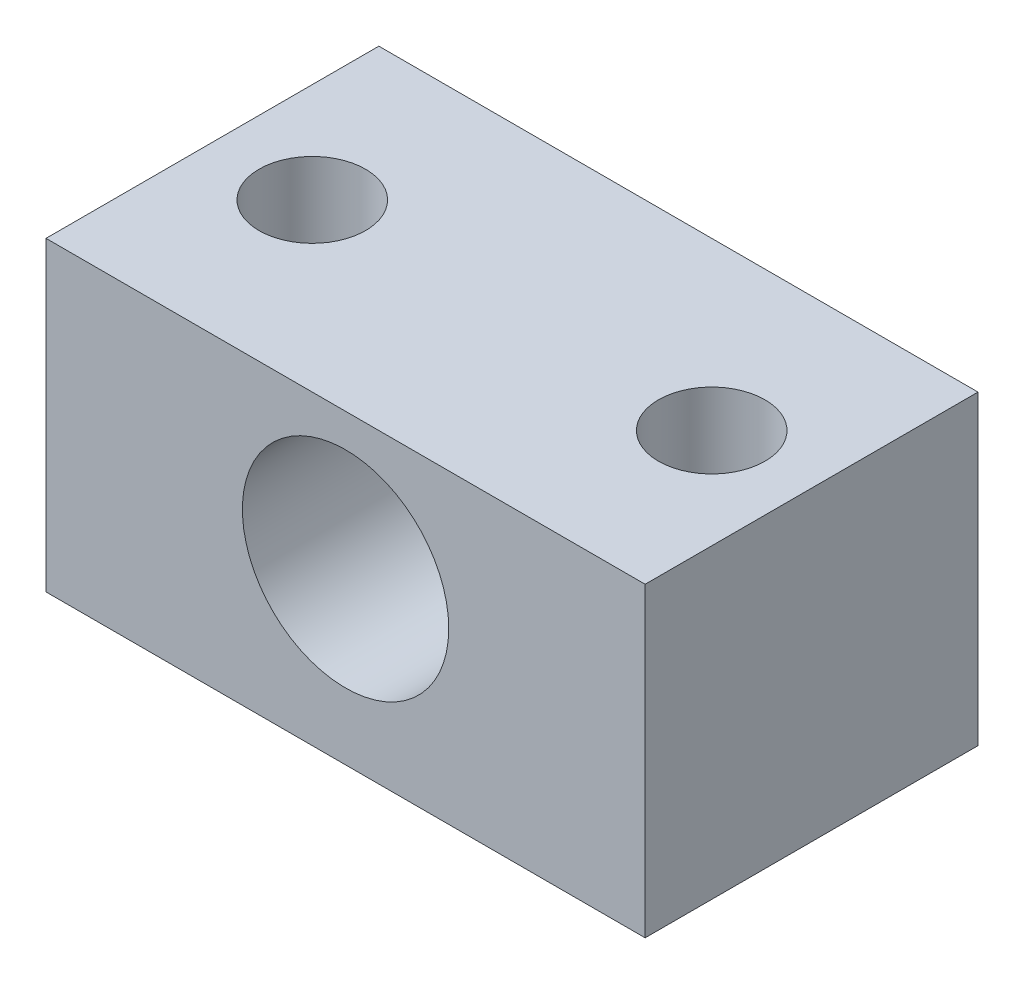
SolidWorks part; units mm, degrees
ref_plane "正面" through (0, 0, 0) normal (0, 0, 1) x (1, 0, 0)
ref_plane "平面" through (0, 0, 0) normal (0, 1, 0) x (1, 0, 0)
ref_plane "右側面" through (0, 0, 0) normal (1, 0, 0) x (0, 0, -1)
sketch "ｽｹｯﾁ1" plane through (0, 0, 0) normal (0, 0, 1) x (1, 0, 0)
  line L0 (0, 0) -> (0, -0.5) construction
  line L1 (9, -5.1) -> (-9, -5.1)
  line L2 (9, -5.1) -> (9, 4.1)
  line L3 (9, 4.1) -> (-9, 4.1)
  line L4 (-9, -5.1) -> (-9, 4.1)
  line L5 (9, -5.1) -> (-9, 4.1) construction
  line L6 (9, 4.1) -> (-9, -5.1) construction
  line L7 (0, 3.1) -> (-9, 3.1) construction
  line L8 (0, -3.1) -> (-9, -3.1) construction
  circle A0 centre (0, 0) radius 3.1
  point P3 (0, -0.5)
  dimension "D1" = 6.2
  dimension "D2" = 1
  dimension "D3" = 2
  dimension "D4" = 18
extrude "ﾎﾞｽ - 押し出し1" add sketch "ｽｹｯﾁ1" along normal blind 10
sketch "ｽｹｯﾁ2" plane through (0, 4.1, 0) normal (0, 1, 0) x (1, 0, 0)
  line L0 (-3.1, -10) -> (3.1, -10) construction
  line L1 (-3.1, -10) -> (3.1, -10) construction
  line L2 (-9, -5) -> (9, -5) construction
  line L3 (-9, -10) -> (-9, 0) construction
  line L4 (9, -10) -> (9, 0) construction
  line L6 (0, 0) -> (0, -10) construction
  circle A0 centre (-6, -5) radius 1.6
  circle A1 centre (6, -5) radius 1.6
  dimension "D1" = 3.2
  dimension "D2" = 12
extrude "ｶｯﾄ - 押し出し1" cut sketch "ｽｹｯﾁ2" against normal blind 10
